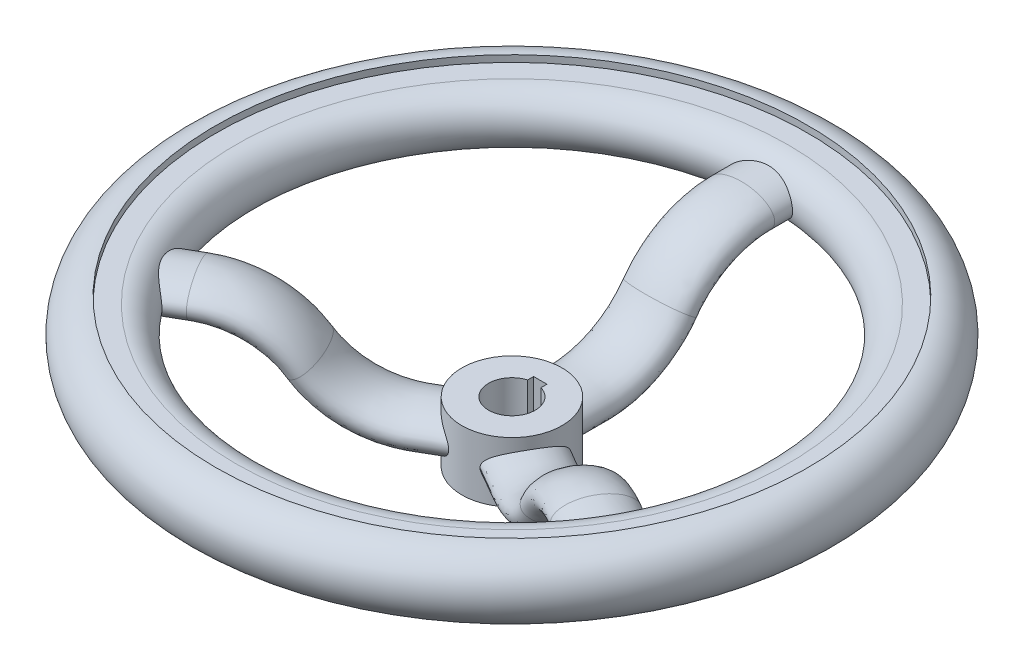
SolidWorks part; units mm, degrees
ref_plane "Plano frontal" through (0, 0, 0) normal (0, 0, 1) x (1, 0, 0)
ref_plane "Plano superior" through (0, 0, 0) normal (0, 1, 0) x (1, 0, 0)
ref_plane "Plano direito" through (0, 0, 0) normal (1, 0, 0) x (0, 0, -1)
sketch "Esboço1" plane through (0, 0, 0) normal (1, 0, 0) x (0, 0, -1)
  line L0 (82.734, 33) -> (88.734, 33)
  line L1 (82.734, 17) -> (88.734, 17)
  line L2 (88.734, 33) -> (88.734, 35)
  line L3 (88.734, 17) -> (88.734, 15)
  line L6 (0, 100) -> (0, -100) construction
  arc A1 (88.734, 15) -> (88.734, 35) centre (88.734, 25) ccw
  arc A2 (82.734, 33) -> (82.734, 17) centre (82.734, 25) ccw
  point P3 (73.1114, 25)
  point P15 (0, 0)
  dimension "D1" = 10
  dimension "D2" = 16
  dimension "D4" = 88.734
  dimension "D3" = 6
  dimension "D8" = 200
  dimension "D9" = 25
revolve "Revolução1" add sketch "Esboço1" angle 360 about L6 region at (0, 25, -87.1338)
sketch3d "3DSketch6"
  line L0 (0, 25, -68.734) -> (0, 25, -88.734)
  line L1 (0, 0, -20) -> (0, 0, 0)
  line L2 (0, 100, 0) -> (0, -100, 0) construction
  arc A0 (0, 25, -68.734) -> (0, 12.5, -44.367) centre (0, -5, -68.734) ccw
  arc A1 (0, 0, -20) -> (0, 12.5, -44.367) centre (0, 30, -20) ccw
  point P1 (0, 25, -68.734)
  point P2 (30, -5, -68.734)
  point P5 (0, 0, -20)
  point P6 (30, 30, -20)
  point P11 (0, 0, 0)
  point P12 (0, 0, 0)
  point P13 (0, -4.0101, 0)
  point P16 (0, 0, 0)
  point P19 (0, 12.5, -44.367)
  dimension "D1" = 60
  dimension "D2" = 20
  dimension "D3" = 20
sketch3d "3DSketch7"
  arc A0 (0, 0, -20) -> (0, 12.5, -44.367) centre (0, 30, -20) ccw construction
  point P3 (30, 30, -20)
sketch "Esboço8" plane through (0, 0, -20) normal (0, 0, 1) x (1, 0, 0)
  ellipse E0 centre (0, 0) end of major axis (-10, 0) minor radius 5.5
  point P1 (0, 0)
  point P7 (0, 0)
  dimension "D1" = 20
  dimension "D2" = 11
sweep "Varredura10" add profiles "Esboço8" path "3DSketch6"
pattern_circular "PadrãoCircular1" count 3 every 120 about axis through (0, 100, 0) along (0, -1, 0) of "Varredura10"
sketch "Esboço9" plane through (0, 0, 0) normal (1, 0, 0) x (0, 0, -1)
  line L0 (0, 9) -> (15, 9)
  line L1 (0, 100) -> (0, -100) construction
  line L2 (15, 9) -> (15, -9)
  line L3 (15, -9) -> (0, -9)
  line L4 (0, -9) -> (0, 9)
  line L5 (7, 9) -> (7, -9)
  dimension "D1" = 15
  dimension "D2" = 18
  dimension "D3" = 7
revolve "Corte-Revolução1" cut sketch "Esboço9" angle 360 about L6 region at (0, 0, -3.5)
revolve "Revolução3" add sketch "Esboço9<4>" angle 360 about L6 region at (0, 0, -11)
sketch "Esboço9<4>" plane through (0, 0, 0) normal (1, 0, 0) x (0, 0, -1) same geometry as "Esboço9"
sketch "Esboço10" plane through (0, 9, 0) normal (0, 1, 0) x (1, 0, 0)
  line L0 (-2, 6.7082) -> (-2, 8.5)
  line L1 (-2, 8.5) -> (2, 8.5)
  line L2 (2, 8.5) -> (2, 6.7082)
  circle A0 centre (0, 0) radius 7 construction
  arc A1 (2, 6.7082) -> (-2, 6.7082) centre (0, 0) ccw
  dimension "D1" = 4
  dimension "D2" = 2
  dimension "D3" = 8.5
extrude "Corte-extrusão1" cut sketch "Esboço10" against normal up to next contours A1 L0 L1 L2
